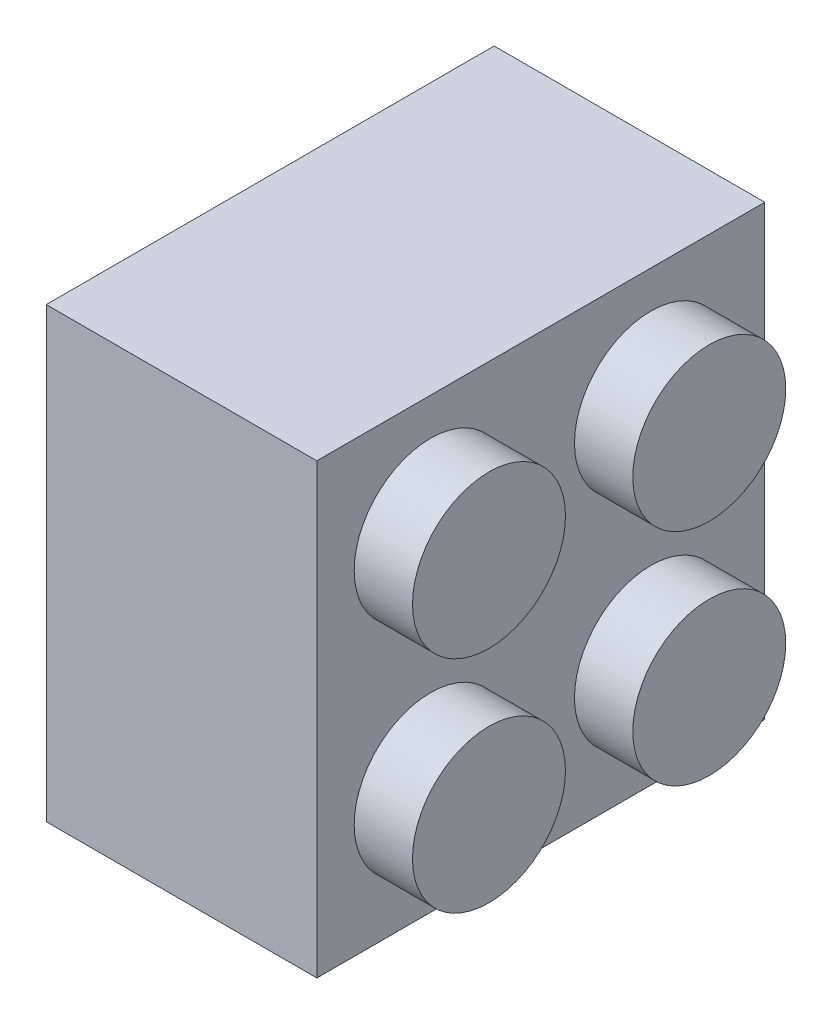
SolidWorks part; units mm, degrees
ref_plane "Plan de face" through (0, 0, 0) normal (0, 0, 1) x (1, 0, 0)
ref_plane "Plan de dessus" through (0, 0, 0) normal (0, 1, 0) x (1, 0, 0)
ref_plane "Plan de droite" through (0, 0, 0) normal (1, 0, 0) x (0, 0, -1)
sketch "Esquisse5" plane through (0, 0, 0) normal (1, 0, 0) x (0, 0, -1)
  line L0 (0, -64.9775) -> (0, 68.6817) construction
  line L1 (-81.1833, 0) -> (80.8746, 0) construction
  line L2 (48, 48) -> (-48, 48)
  line L3 (-48, 48) -> (-48, -48)
  line L4 (-48, -48) -> (48, -48)
  line L5 (48, -48) -> (48, 48)
  line L6 (40, 40) -> (-40, 40)
  line L7 (-40, 40) -> (-40, -40)
  line L8 (-40, -40) -> (40, -40)
  line L9 (40, -40) -> (40, 40)
  point P7 (0, 0)
  point P10 (0, 0)
  dimension "D1" = 96
  dimension "D2" = 8
extrude "Boss.-Extru.1" add sketch "Esquisse5" along normal blind 48
sketch "Esquisse6" plane through (48, 0, 0) normal (1, 0, 0) x (0, 0, -1)
  line L1 (-48, 48) -> (48, 48)
  line L2 (-48, 48) -> (-48, -48)
  line L3 (-48, -48) -> (48, -48)
  line L4 (48, 48) -> (48, -48)
extrude "Boss.-Extru.3" add sketch "Esquisse6" along normal offset from surface (10 mm away) 58 up to face at (0, 0, 0)
sketch "Esquisse7" plane through (58, 0, 0) normal (1, 0, 0) x (0, 0, -1)
  line L0 (-48, 48) -> (48, -48) construction
  line L1 (-48, -48) -> (48, 48) construction
  line L2 (40, 23.6081) -> (40, -23.6081) construction
  line L3 (48, -48) -> (48, 48) construction
  circle A0 centre (23.6081, 23.6081) radius 16.3919
  circle A1 centre (23.6081, -23.6081) radius 16.3919
  circle A2 centre (-23.6081, -23.6081) radius 16.3919
  circle A3 centre (-23.6081, 23.6081) radius 16.3919
  point P19 (0, 0)
  point P20 (0, 0)
  dimension "D1" = 4
  dimension "D2" = 8
extrude "Boss.-Extru.4" add sketch "Esquisse7" along normal blind 12.5
sketch "Esquisse8" plane through (0, 0, 0) normal (-1, 0, 0) x (0, 0, 1)
  line L0 (-48, 48) -> (48, -48) construction
  line L1 (-48, -48) -> (48, 48) construction
  circle A0 centre (0, 0) radius 18.5
  circle A1 centre (0, 0) radius 11.5
  dimension "D1" = 7
  dimension "D2" = 23
extrude "Boss.-Extru.5" add sketch "Esquisse8" against normal up to surface (48 mm away) up to face at (48, 0, 0)
chamfer "Chanfrein2" distance 48 angle 5 1 edges at (48, 0, -18.5) first distance on face at (0, 0, 18.5)
